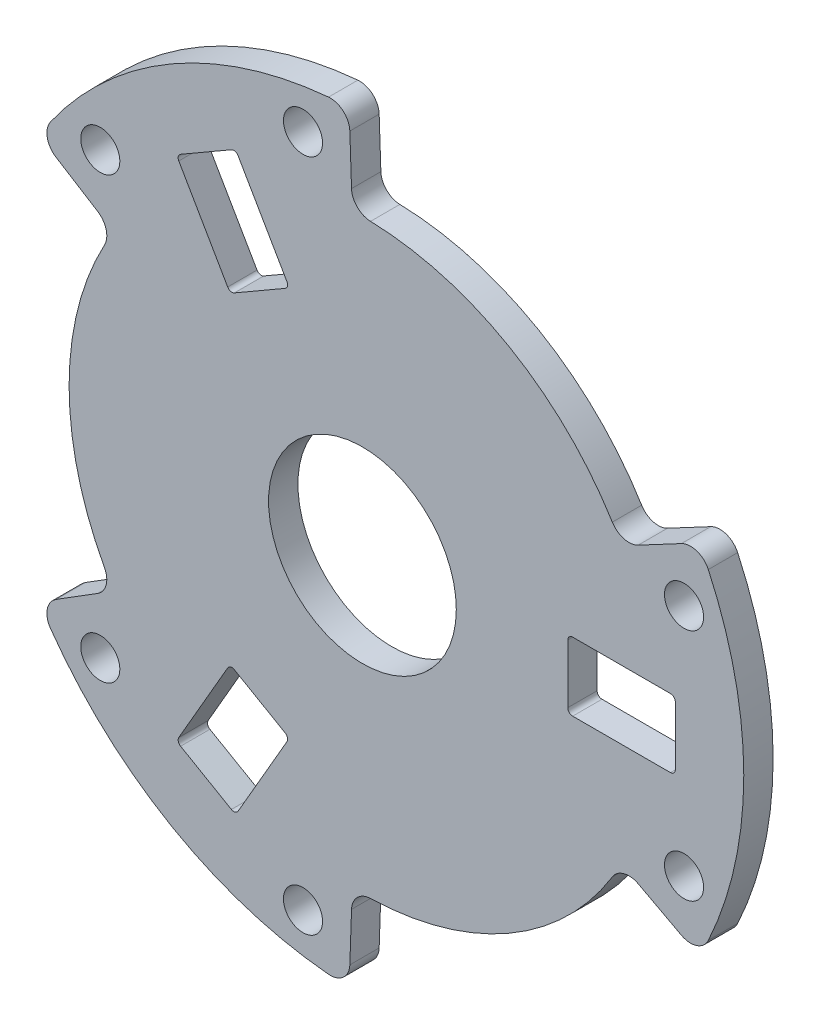
SolidWorks part; units mm, degrees
material "ABS PC"
ref_plane "Front Plane" through (0, 0, 0) normal (0, 0, 1) x (1, 0, 0)
ref_plane "Top Plane" through (0, 0, 0) normal (0, 1, 0) x (1, 0, 0)
ref_plane "Right Plane" through (0, 0, 0) normal (1, 0, 0) x (0, 0, -1)
sketch "Sketch1" plane through (0, 0, 0) normal (0, 0, 1) x (1, 0, 0)
  line L0 (-30.4485, 16.9243) -> (-34.6959, 19.5783)
  line L1 (-22.1451, 25.5298) -> (-17.1451, 16.8695)
  line L2 (-16.462, 16.6865) -> (-11.2659, 19.6865)
  line L3 (-11.0829, 20.3695) -> (-16.0829, 29.0298)
  line L4 (-16.7659, 29.2128) -> (-21.962, 26.2128)
  line L5 (-4.4786, 31.918) -> (-4.6534, 36.9234)
  line L6 (-30.4485, -16.9243) -> (-34.6959, -19.5783)
  line L7 (-4.4786, -31.918) -> (-4.6534, -36.9234)
  line L8 (28.136, 3.5) -> (18.136, 3.5)
  line L9 (17.636, 3) -> (17.636, -3)
  line L10 (18.136, -3.5) -> (28.136, -3.5)
  line L11 (28.636, -3) -> (28.636, 3)
  line L12 (-16.0829, -29.0298) -> (-11.0829, -20.3695)
  line L13 (-11.2659, -19.6865) -> (-16.462, -16.6865)
  line L14 (-17.1451, -16.8695) -> (-22.1451, -25.5298)
  line L15 (-21.962, -26.2128) -> (-16.7659, -29.2128)
  line L16 (24.8351, -14.9937) -> (29.2573, -17.3451)
  line L17 (24.8351, 14.9937) -> (29.2573, 17.3451)
  line L18 (-30.4485, 16.9243) -> (-34.6959, 19.5783)
  line L19 (-22.1451, 25.5298) -> (-17.1451, 16.8695)
  line L20 (-16.462, 16.6865) -> (-11.2659, 19.6865)
  line L21 (-11.0829, 20.3695) -> (-16.0829, 29.0298)
  line L22 (-16.7659, 29.2128) -> (-21.962, 26.2128)
  line L23 (-4.4786, 31.918) -> (-4.6534, 36.9234)
  line L24 (-30.4485, -16.9243) -> (-34.6959, -19.5783)
  line L25 (-4.4786, -31.918) -> (-4.6534, -36.9234)
  line L26 (28.136, 3.5) -> (18.136, 3.5)
  line L27 (17.636, 3) -> (17.636, -3)
  line L28 (18.136, -3.5) -> (28.136, -3.5)
  line L29 (28.636, -3) -> (28.636, 3)
  line L30 (-16.0829, -29.0298) -> (-11.0829, -20.3695)
  line L31 (-11.2659, -19.6865) -> (-16.462, -16.6865)
  line L32 (-17.1451, -16.8695) -> (-22.1451, -25.5298)
  line L33 (-21.962, -26.2128) -> (-16.7659, -29.2128)
  line L34 (24.8351, -14.9937) -> (29.2573, -17.3451)
  line L35 (24.8351, 14.9937) -> (29.2573, 17.3451)
  circle A0 centre (-30.1755, 22.4976) radius 2
  arc A1 (-6.8299, 38.8457) -> (-35.2724, 22.4244) centre (-3.364, 0) ccw
  arc A2 (-35.2724, 22.4244) -> (-34.6959, 19.5783) centre (-33.636, 21.2744) ccw
  arc A3 (-29.7493, 14.2764) -> (-30.4485, 16.9243) centre (-31.5083, 15.2282) ccw
  arc A4 (-29.7493, 14.2764) -> (-29.7493, -14.2764) centre (-3.364, 0) ccw
  arc A5 (-17.1451, 16.8695) -> (-16.462, 16.6865) centre (-16.712, 17.1195) ccw
  arc A6 (-11.2659, 19.6865) -> (-11.0829, 20.3695) centre (-11.5159, 20.1195) ccw
  arc A7 (-16.0829, 29.0298) -> (-16.7659, 29.2128) centre (-16.5159, 28.7798) ccw
  arc A8 (-21.962, 26.2128) -> (-22.1451, 25.5298) centre (-21.712, 25.7798) ccw
  circle A9 centre (-9.4417, 34.4683) radius 2
  arc A10 (-4.6534, 36.9234) -> (-6.8299, 38.8457) centre (-6.6521, 36.8536) ccw
  arc A11 (-4.4786, 31.918) -> (-2.535, 29.9885) centre (-2.4798, 31.9878) ccw
  arc A12 (22.1924, 15.7121) -> (-2.535, 29.9885) centre (-3.364, 0) ccw
  circle A13 centre (-3.364, 0) radius 9.6
  arc A14 (-30.4485, -16.9243) -> (-29.7493, -14.2764) centre (-31.5083, -15.2282) ccw
  circle A15 centre (-30.1755, -22.4976) radius 2
  arc A16 (-34.6959, -19.5783) -> (-35.2724, -22.4244) centre (-33.636, -21.2744) ccw
  arc A17 (-35.2724, -22.4244) -> (-6.8299, -38.8457) centre (-3.364, 0) ccw
  circle A18 centre (-9.4417, -34.4683) radius 2
  arc A19 (-6.8299, -38.8457) -> (-4.6534, -36.9234) centre (-6.6521, -36.8536) ccw
  arc A20 (-2.535, -29.9885) -> (-4.4786, -31.918) centre (-2.4798, -31.9878) ccw
  arc A21 (-2.535, -29.9885) -> (22.1924, -15.7121) centre (-3.364, 0) ccw
  arc A22 (18.136, 3.5) -> (17.636, 3) centre (18.136, 3) ccw
  arc A23 (17.636, -3) -> (18.136, -3.5) centre (18.136, -3) ccw
  arc A24 (28.136, -3.5) -> (28.636, -3) centre (28.136, -3) ccw
  arc A25 (28.636, 3) -> (28.136, 3.5) centre (28.136, 3) ccw
  arc A26 (-11.0829, -20.3695) -> (-11.2659, -19.6865) centre (-11.5159, -20.1195) ccw
  arc A27 (-16.462, -16.6865) -> (-17.1451, -16.8695) centre (-16.712, -17.1195) ccw
  arc A28 (-22.1451, -25.5298) -> (-21.962, -26.2128) centre (-21.712, -25.7798) ccw
  arc A29 (-16.7659, -29.2128) -> (-16.0829, -29.0298) centre (-16.5159, -28.7798) ccw
  arc A30 (24.8351, -14.9937) -> (22.1924, -15.7121) centre (23.8962, -16.7596) ccw
  arc A31 (29.2573, -17.3451) -> (32.0103, -16.4213) centre (30.1963, -15.5792) ccw
  arc A32 (32.0103, -16.4213) -> (32.0103, 16.4213) centre (-3.364, 0) ccw
  circle A33 centre (29.5253, -11.9707) radius 2
  circle A34 centre (29.5253, 11.9707) radius 2
  arc A35 (32.0103, 16.4213) -> (29.2573, 17.3451) centre (30.1963, 15.5792) ccw
  arc A36 (22.1924, 15.7121) -> (24.8351, 14.9937) centre (23.8962, 16.7596) ccw
  circle A38 centre (-3.364, 0) radius 9.6
  circle A39 centre (-30.1755, 22.4976) radius 2
  arc A40 (-6.8299, 38.8457) -> (-35.2724, 22.4244) centre (-3.364, 0) ccw
  arc A41 (-35.2724, 22.4244) -> (-34.6959, 19.5783) centre (-33.636, 21.2744) ccw
  arc A42 (-29.7493, 14.2764) -> (-30.4485, 16.9243) centre (-31.5083, 15.2282) ccw
  arc A43 (-29.7493, 14.2764) -> (-29.7493, -14.2764) centre (-3.364, 0) ccw
  arc A44 (-17.1451, 16.8695) -> (-16.462, 16.6865) centre (-16.712, 17.1195) ccw
  arc A45 (-11.2659, 19.6865) -> (-11.0829, 20.3695) centre (-11.5159, 20.1195) ccw
  arc A46 (-16.0829, 29.0298) -> (-16.7659, 29.2128) centre (-16.5159, 28.7798) ccw
  arc A47 (-21.962, 26.2128) -> (-22.1451, 25.5298) centre (-21.712, 25.7798) ccw
  circle A48 centre (-9.4417, 34.4683) radius 2
  arc A49 (-4.6534, 36.9234) -> (-6.8299, 38.8457) centre (-6.6521, 36.8536) ccw
  arc A50 (-4.4786, 31.918) -> (-2.535, 29.9885) centre (-2.4798, 31.9878) ccw
  arc A51 (22.1924, 15.7121) -> (-2.535, 29.9885) centre (-3.364, 0) ccw
  circle A52 centre (-3.364, 0) radius 9.6
  arc A53 (-30.4485, -16.9243) -> (-29.7493, -14.2764) centre (-31.5083, -15.2282) ccw
  circle A54 centre (-30.1755, -22.4976) radius 2
  arc A55 (-34.6959, -19.5783) -> (-35.2724, -22.4244) centre (-33.636, -21.2744) ccw
  arc A56 (-35.2724, -22.4244) -> (-6.8299, -38.8457) centre (-3.364, 0) ccw
  circle A57 centre (-9.4417, -34.4683) radius 2
  arc A58 (-6.8299, -38.8457) -> (-4.6534, -36.9234) centre (-6.6521, -36.8536) ccw
  arc A59 (-2.535, -29.9885) -> (-4.4786, -31.918) centre (-2.4798, -31.9878) ccw
  arc A60 (-2.535, -29.9885) -> (22.1924, -15.7121) centre (-3.364, 0) ccw
  arc A61 (18.136, 3.5) -> (17.636, 3) centre (18.136, 3) ccw
  arc A62 (17.636, -3) -> (18.136, -3.5) centre (18.136, -3) ccw
  arc A63 (28.136, -3.5) -> (28.636, -3) centre (28.136, -3) ccw
  arc A64 (28.636, 3) -> (28.136, 3.5) centre (28.136, 3) ccw
  arc A65 (-11.0829, -20.3695) -> (-11.2659, -19.6865) centre (-11.5159, -20.1195) ccw
  arc A66 (-16.462, -16.6865) -> (-17.1451, -16.8695) centre (-16.712, -17.1195) ccw
  arc A67 (-22.1451, -25.5298) -> (-21.962, -26.2128) centre (-21.712, -25.7798) ccw
  arc A68 (-16.7659, -29.2128) -> (-16.0829, -29.0298) centre (-16.5159, -28.7798) ccw
  arc A69 (24.8351, -14.9937) -> (22.1924, -15.7121) centre (23.8962, -16.7596) ccw
  arc A70 (29.2573, -17.3451) -> (32.0103, -16.4213) centre (30.1963, -15.5792) ccw
  arc A71 (32.0103, -16.4213) -> (32.0103, 16.4213) centre (-3.364, 0) ccw
  circle A72 centre (29.5253, -11.9707) radius 2
  circle A73 centre (29.5253, 11.9707) radius 2
  arc A74 (32.0103, 16.4213) -> (29.2573, 17.3451) centre (30.1963, 15.5792) ccw
  arc A75 (22.1924, 15.7121) -> (24.8351, 14.9937) centre (23.8962, 16.7596) ccw
  circle A77 centre (-3.364, 0) radius 9.6
extrude "Boss-Extrude1" add sketch "Sketch1" along normal blind 3 contours A36 A12 A11 L5 A10 A1 A2 L0 A3 A4 A14 L6 A16 A17 A19 L7 A20 A21 A30 L16 A31 A32 A35 L17 A34 A33 A29 L15 A28 L14 A27 L13 A26 L12 A25 L11 A24 L10 A23 L9 A22 L8 A18 A15 region at (-32.0134, 19.1455, 0)
